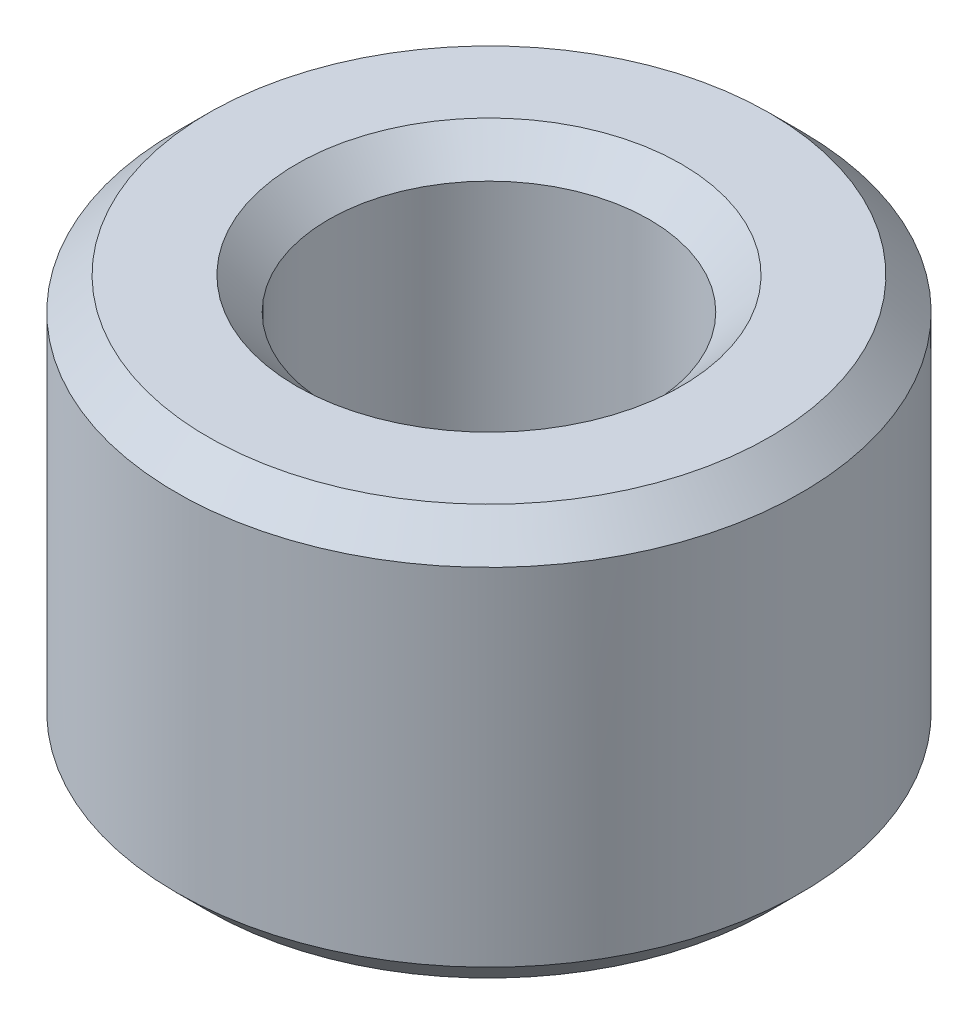
SolidWorks part; units mm, degrees
ref_plane "Front Plane" through (0, 0, 0) normal (0, 0, 1) x (1, 0, 0)
ref_plane "Top Plane" through (0, 0, 0) normal (0, 1, 0) x (1, 0, 0)
ref_plane "Right Plane" through (0, 0, 0) normal (1, 0, 0) x (0, 0, -1)
sketch "Sketch1" plane through (0, 0, 0) normal (0, 1, 0) x (1, 0, 0)
  circle A0 centre (0, 0) radius 32.5
  dimension "SLEEVE_OD" = 65
extrude "Boss-Extrude1" add sketch "Sketch1" along normal blind 42.6468
sketch "Sketch2" plane through (0, 0, 0) normal (0, 1, 0) x (1, 0, 0)
  circle A0 centre (0, 0) radius 16.6689
  dimension "BORE_D" = 33.3378
extrude "Cut-Extrude1" cut sketch "Sketch2" along normal through all
chamfer "Chamfer1" distance 3.3286 angle 45 4 edges at (0, 42.6468, 16.6689) (0, 0, 16.6689) (0, 0, 32.5) (0, 42.6468, 32.5)
